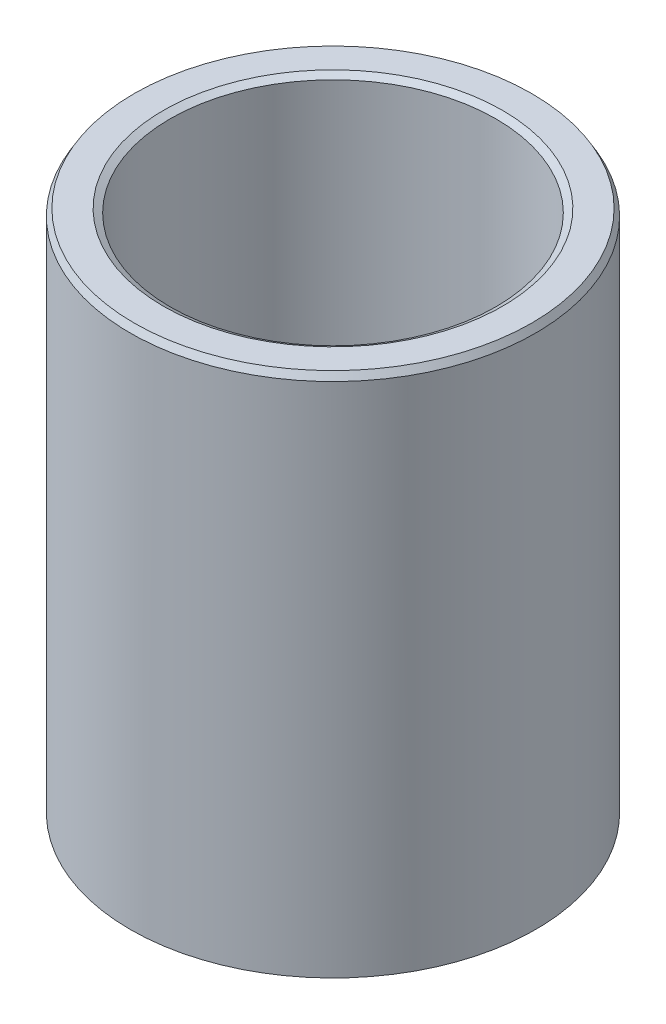
SolidWorks part; units mm, degrees
ref_plane "Front Plane" through (0, 0, 0) normal (0, 0, 1) x (1, 0, 0)
ref_plane "Top Plane" through (0, 0, 0) normal (0, 1, 0) x (1, 0, 0)
ref_plane "Right Plane" through (0, 0, 0) normal (1, 0, 0) x (0, 0, -1)
sketch "Sketch1" plane through (0, 0, 0) normal (0, 1, 0) x (1, 0, 0)
  circle A0 centre (0, 0) radius 60
  dimension "SLEEVE_OD" = 120
extrude "Boss-Extrude1" add sketch "Sketch1" along normal blind 156.0563
sketch "Sketch2" plane through (0, 0, 0) normal (0, 1, 0) x (1, 0, 0)
  circle A0 centre (0, 0) radius 48.2214
  dimension "BORE_D" = 96.4427
extrude "Cut-Extrude1" cut sketch "Sketch2" along normal through all
chamfer "Chamfer1" distance 1.9959 angle 30 4 edges at (0, 156.0563, 48.2214) (0, 0, 48.2214) (0, 0, 60) (0, 156.0563, 60) first distance on face at (0, 156.0563, 48.2214) first distance on face at (0, 0, 48.2214) first distance on face at (0, 156.0563, 60)
